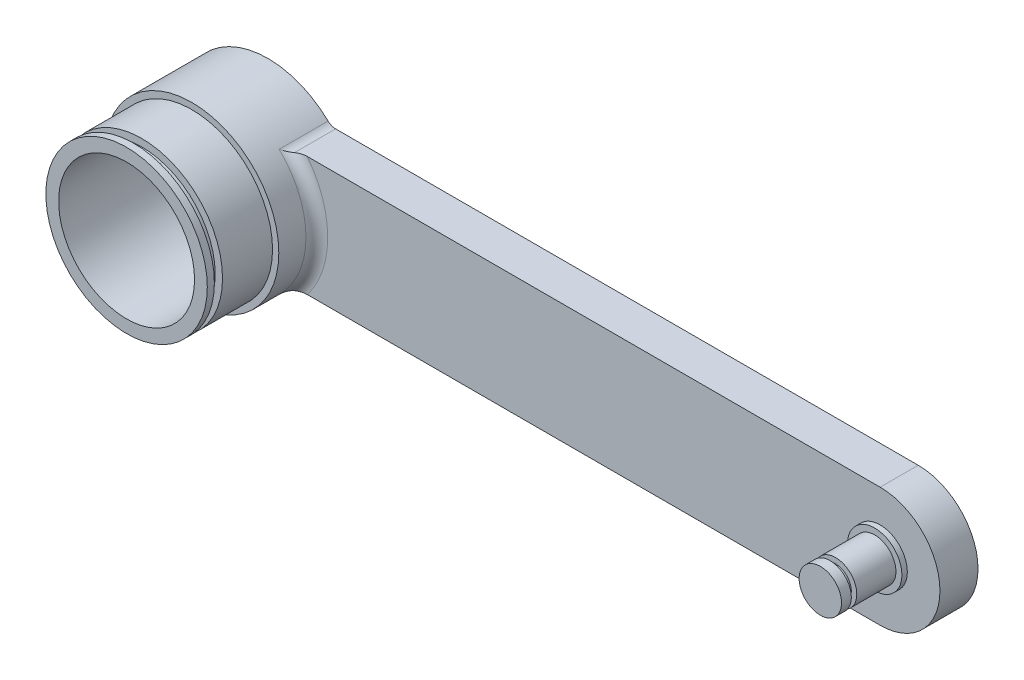
SolidWorks part; units mm, degrees
ref_plane "前视基准面" through (0, 0, 0) normal (0, 0, 1) x (1, 0, 0)
ref_plane "上视基准面" through (0, 0, 0) normal (0, 1, 0) x (1, 0, 0)
ref_plane "右视基准面" through (0, 0, 0) normal (1, 0, 0) x (0, 0, -1)
sketch "草图1" plane through (0, 0, 0) normal (0, 0, 1) x (1, 0, 0)
  line L3 (119.6096, 11) -> (11.619, 11)
  line L4 (119.6096, -11) -> (11.619, -11)
  arc A1 (11.619, 11) -> (11.619, -11) centre (0, 0) ccw
  arc A2 (119.6096, -11) -> (119.6096, 11) centre (119.6096, 0) ccw
extrude "凸台-拉伸1" add sketch "草图1" along normal blind 7
sketch "草图2" plane through (0, 0, 7) normal (0, 0, 1) x (1, 0, 0)
  circle A0 centre (0, 0) radius 6.7
extrude "切除-拉伸1" cut sketch "草图2" against normal blind 7
sketch "草图3" plane through (0, 0, 7) normal (0, 0, 1) x (1, 0, 0)
  circle A0 centre (0, 0) radius 6.7
  circle A1 centre (0, 0) radius 12.5
  dimension "D1" = 25
extrude "切除-拉伸2" cut sketch "草图3" against normal blind 5
sketch "草图4" plane through (0, 0, 7) normal (0, 0, 1) x (1, 0, 0)
  circle A0 centre (0, 0) radius 12.5
  circle A1 centre (0, 0) radius 16
  dimension "D1" = 25
extrude "凸台-拉伸2" add sketch "草图4" along normal blind 7
sketch "草图5" plane through (0, 0, 14) normal (0, 0, 1) x (1, 0, 0)
  circle A0 centre (0, 0) radius 12.5
  circle A1 centre (0, 0) radius 14.85
  dimension "D1" = 25
extrude "凸台-拉伸3" add sketch "草图5" along normal blind 12
sketch "草图6" plane through (0, 0, 7) normal (0, 0, 1) x (1, 0, 0)
  circle A0 centre (119.6096, 0) radius 5
extrude "凸台-拉伸4" add sketch "草图6" along normal blind 1
sketch "草图7" plane through (0, 0, 8) normal (0, 0, 1) x (1, 0, 0)
  circle A0 centre (119.6096, 0) radius 3.9
extrude "凸台-拉伸5" add sketch "草图7" along normal blind 10
fillet "圆角1" radius 2 3 edges at (11.619, -11, 3.5) (11.619, 11, 3.5) (16, 0, 7)
sketch "草图8" plane through (0, 0, 0) normal (0, 0, -1) x (-1, 0, 0)
  circle A1 centre (0, -9.5) radius 1.5
  circle A2 centre (-8.2272, 4.75) radius 1.5
  circle A3 centre (8.2272, 4.75) radius 1.5
  point P11 (0, 0)
  dimension "D1" = 3
extrude "切除-拉伸3" cut sketch "草图8" against normal blind 10
ref_plane "基准面1" through (0, 0, 23.2) normal (0, 0, 1) x (1, 0, 0)
sketch "草图9" plane through (0, 0, 23.2) normal (0, 0, 1) x (1, 0, 0)
  circle A0 centre (0, 0) radius 14.85
  circle A1 centre (0, 0) radius 13.5
extrude "切除-拉伸4" cut sketch "草图9" along normal blind 1.5
ref_plane "基准面2" through (0, 0, 15.2) normal (0, 0, 1) x (1, 0, 0)
sketch "草图10" plane through (0, 0, 15.2) normal (0, 0, 1) x (1, 0, 0)
  circle A0 centre (119.6096, 0) radius 3.9
  circle A1 centre (119.6096, 0) radius 2.9
extrude "切除-拉伸5" cut sketch "草图10" along normal blind 1
